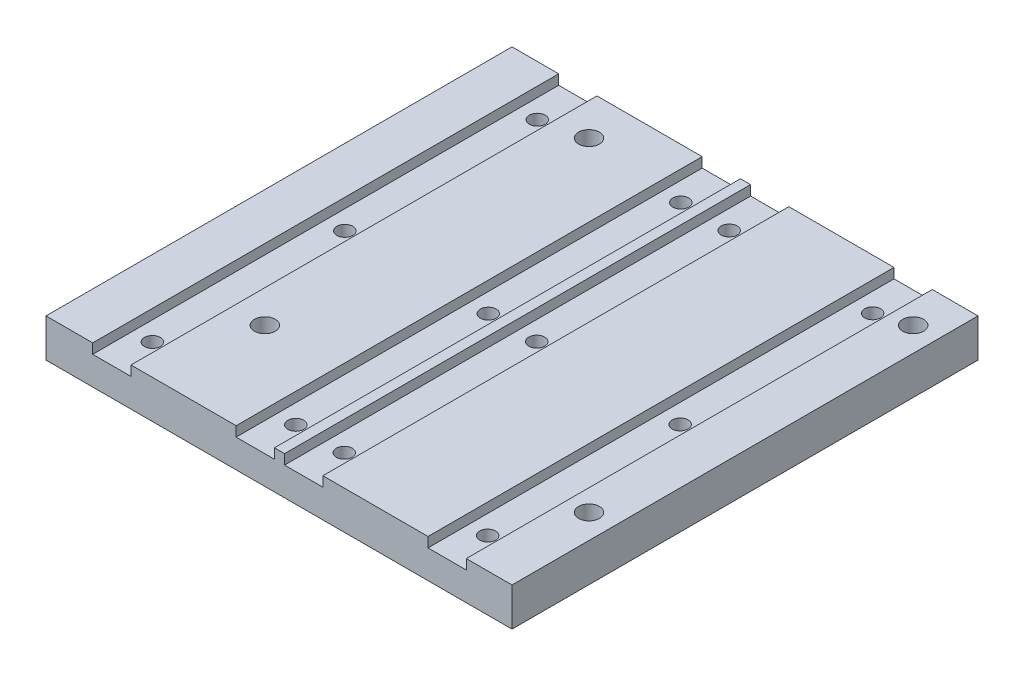
SolidWorks part; units mm, degrees
material "Acrylic (Medium-high impact)"
ref_plane "Front Plane" through (0, 0, 0) normal (0, 0, 1) x (1, 0, 0)
ref_plane "Top Plane" through (0, 0, 0) normal (0, 1, 0) x (1, 0, 0)
ref_plane "Right Plane" through (0, 0, 0) normal (1, 0, 0) x (0, 0, -1)
sketch "Sketch1" plane through (0, 0, 0) normal (0, 1, 0) x (1, 0, 0)
  line L1 (73.025, 73.025) -> (-73.025, 73.025)
  line L2 (73.025, 73.025) -> (73.025, -73.025)
  line L3 (73.025, -73.025) -> (-73.025, -73.025)
  line L4 (-73.025, 73.025) -> (-73.025, -73.025)
  line L5 (73.025, 73.025) -> (-73.025, -73.025) construction
  line L6 (73.025, -73.025) -> (-73.025, 73.025) construction
  line L7 (-36.195, 60.325) -> (65.405, 60.325) construction
  line L8 (-36.195, 60.325) -> (-36.195, -41.275) construction
  line L9 (-36.195, -41.275) -> (65.405, -41.275) construction
  line L10 (65.405, 60.325) -> (65.405, -41.275) construction
  line L11 (-36.195, 60.325) -> (65.405, -41.275) construction
  line L12 (-36.195, -41.275) -> (65.405, 60.325) construction
  point P0 (0, 0)
  point P6 (14.605, 9.525)
  dimension "D1" = 146.05
  dimension "D2" = 146.05
  dimension "D3" = 101.6
  dimension "D4" = 7.62
  dimension "D5" = 12.7
extrude "Boss-Extrude1" add sketch "Sketch1" against normal blind 12
hole_wizard "1/4 Clearance Hole1" positions "Sketch2" profile "Sketch3" hole size "1/4" standard "ANSI Inch" end condition through all
sketch "Sketch2" plane through (0, 0, 0) normal (0, 1, 0) x (1, 0, 0)
  point P0 (-36.195, 60.325)
  point P3 (-36.195, -41.275)
  point P6 (65.405, -41.275)
  point P9 (65.405, 60.325)
sketch "Sketch3" plane through (-36.195, 0, -60.325) normal (1, 0, 0) x (0, 0, 1)
  line L0 (0, 0) -> (0, 12)
  line L1 (0, 12) -> (3.2639, 12)
  line L2 (3.2639, 12) -> (3.2639, 0)
  line L5 (3.2639, 0) -> (0, 0)
  line L11 (0, -6.35) -> (0, 107.95) construction
  dimension "Thru Hole Dia." = 6.5278
  dimension "Thru Hole Depth" = 12
sketch "Sketch4" plane through (0, 0, 73.025) normal (0, 0, 1) x (1, 0, 0)
  line L0 (-73.025, 0) -> (73.025, 0) construction
  line L1 (46.705, -3.11) -> (58.705, -3.11)
  line L2 (46.705, -3.11) -> (46.705, 0)
  line L3 (46.705, 0) -> (58.705, 0)
  line L4 (58.705, -3.11) -> (58.705, 0)
  line L5 (46.705, -3.11) -> (58.705, 0) construction
  line L6 (46.705, 0) -> (58.705, -3.11) construction
  line L7 (73.025, -12) -> (73.025, 0) construction
  line L8 (-73.025, -12) -> (73.025, -12) construction
  point P0 (52.705, -1.555)
  dimension "D1" = 8.89
  dimension "D2" = 12
  dimension "D3" = 20.32
extrude "Cut-Extrude1" cut sketch "Sketch4" against normal through all
sketch "Sketch6" plane through (0, -12, 0) normal (0, -1, 0) x (1, 0, 0)
  line L0 (52.705, 60.325) -> (52.705, -60.325) construction
  line L1 (46.705, 73.025) -> (58.705, 73.025) construction
  line L2 (73.025, 73.025) -> (73.025, -73.025) construction
  line L3 (46.705, -73.025) -> (-73.025, -73.025) construction
  point P5 (52.705, 73.025)
  point P8 (73.025, 0)
  point P10 (52.705, 0)
  dimension "D1" = 12.7
hole_wizard "CBORE for #10 Socket Head Cap Screw1" positions "Sketch9" profile "Sketch8" counterbore size "#10" standard "ANSI Inch" end condition through all
sketch "Sketch9" plane through (0, -12, 0) normal (0, -1, 0) x (-1, 0, 0)
  point P0 (-52.705, -60.325)
  point P3 (-52.705, 60.325)
  point P7 (-52.705, 0)
sketch "Sketch8" plane through (52.705, -12, 60.325) normal (1, 0, 0) x (0, 0, -1)
  line L0 (0, 0) -> (0, 12)
  line L1 (0, 12) -> (2.4892, 12)
  line L3 (2.4892, 12) -> (2.4892, 5.08)
  line L4 (2.4892, 5.08) -> (4.7625, 5.08)
  line L5 (4.7625, 5.08) -> (4.7625, 0)
  line L7 (4.7625, 0) -> (0, 0)
  line L11 (0, -6.35) -> (0, 107.95) construction
  dimension "Thru Hole Dia." = 4.9784
  dimension "Thru Hole Depth" = 12
  dimension "C'Bore Dia." = 9.525
  dimension "C'Bore Depth" = 5.08
pattern_linear "LPattern1" count 2 spacing 44.958 along (-1, 0, 0) count 2 spacing 60.133 along (-1, 0, 0) of "Cut-Extrude1", "CBORE for #10 Socket Head Cap Screw1"
